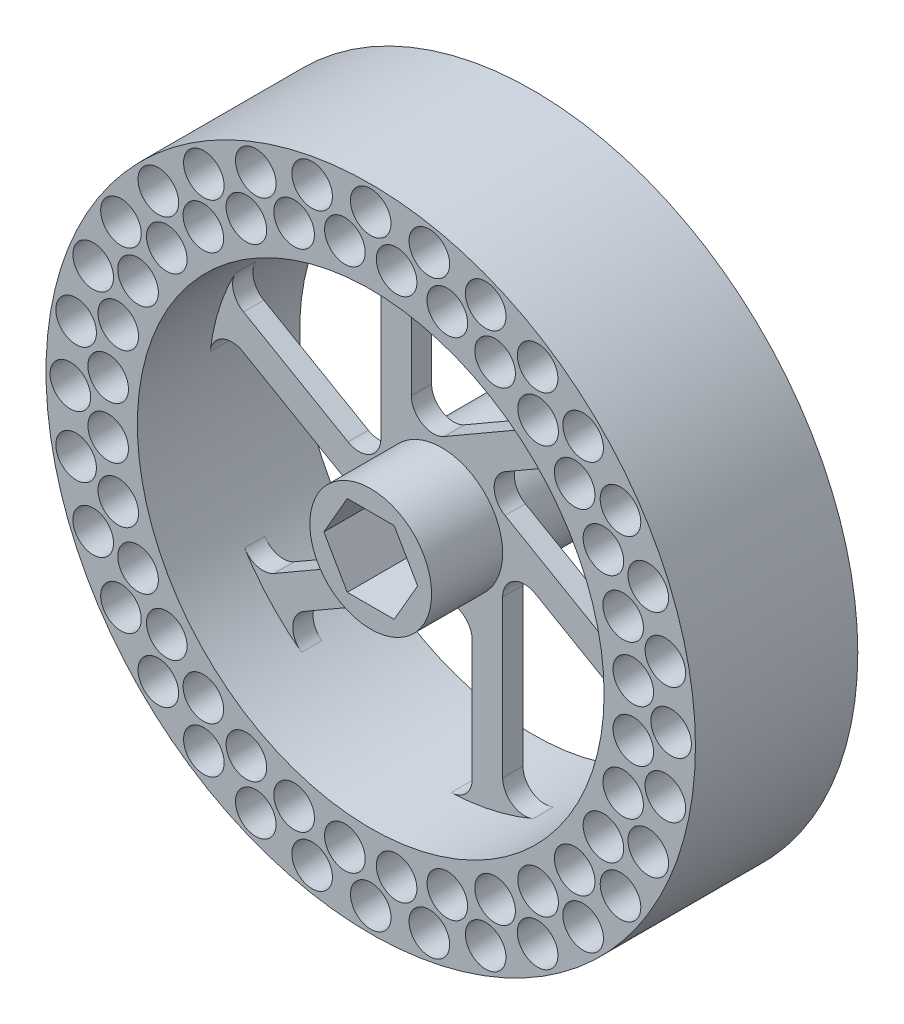
SolidWorks part; units mm, degrees
ref_plane "Front Plane" through (0, 0, 0) normal (0, 0, 1) x (1, 0, 0)
ref_plane "Top Plane" through (0, 0, 0) normal (0, 1, 0) x (1, 0, 0)
ref_plane "Right Plane" through (0, 0, 0) normal (1, 0, 0) x (0, 0, -1)
sketch "Sketch1" plane through (0, 0, 0) normal (0, 0, 1) x (1, 0, 0)
  line L1 (-3.6662, 6.35) -> (-7.3323, 0)
  line L2 (-7.3323, 0) -> (-3.6662, -6.35)
  line L3 (-3.6662, -6.35) -> (3.6662, -6.35)
  line L4 (3.6662, -6.35) -> (7.3323, 0)
  line L5 (7.3323, 0) -> (3.6662, 6.35)
  line L6 (3.6662, 6.35) -> (-3.6662, 6.35)
  circle A0 centre (0, 0) radius 6.35 construction
  circle A1 centre (0, 0) radius 46.9945 construction
  circle A2 centre (0, 0) radius 50.8
  dimension "D1" = 93.9889
  dimension "D2" = 101.6
  dimension "D3" = 12.7
extrude "Boss-Extrude1" add sketch "Sketch1" along normal mid plane 25.4
sketch "Sketch2" plane through (0, 0, 12.7) normal (0, 0, 1) x (1, 0, 0)
  circle A0 centre (0, 46.9945) radius 3.175
  circle A1 centre (0, 0) radius 46.9945 construction
  dimension "D1" = 6.35
extrude "Cut-Extrude1" cut sketch "Sketch2" against normal through all
pattern_circular "CirPattern1" count 32 over 360 about axis through (0, 0, 12.7) along (0, 0, -1) of "Cut-Extrude1"
sketch "Sketch3" plane through (0, 0, 12.7) normal (0, 0, 1) x (1, 0, 0)
  line L0 (0, 46.9945) -> (4.0457, 41.0762) construction
  line L1 (4.0457, 41.0762) -> (9.1682, 46.0915) construction
  circle A0 centre (4.0457, 41.0762) radius 3.175
  circle A1 centre (9.1682, 46.0915) radius 3.175 construction
  circle A2 centre (0, 0) radius 41.275 construction
  dimension "D1" = 82.55
extrude "Cut-Extrude2" cut sketch "Sketch3" against normal through all
pattern_circular "CirPattern2" count 32 every 11.25 about axis through (0, 0, 12.7) along (0, 0, -1) of "Cut-Extrude2"
sketch "Sketch4" plane through (0, 0, 12.7) normal (0, 0, 1) x (1, 0, 0)
  circle A0 centre (0, 0) radius 36.5125
  circle A1 centre (0, 0) radius 9.525
  dimension "D1" = 73.025
  dimension "D2" = 19.05
extrude "Cut-Extrude3" cut sketch "Sketch4" against normal through all
sketch "Sketch5" plane through (0, 0, 0) normal (0, 0, 1) x (1, 0, 0)
  line L0 (-9.525, 0) -> (-9.525, 35.2482)
  line L1 (-4.7625, 8.2489) -> (-4.7625, 36.2006)
  circle A0 centre (0, 0) radius 9.525 construction
  circle A1 centre (0, 0) radius 36.5125 construction
  arc A2 (-4.7625, 36.2006) -> (-9.525, 35.2482) centre (0, 0) ccw
  arc A3 (-4.7625, 8.2489) -> (-9.525, 0) centre (0, 0) ccw
  dimension "D1" = 4.7625
extrude "Boss-Extrude2" add sketch "Sketch5" along normal mid plane 3.175
pattern_circular "CirPattern3" count 6 over 360 about axis through (0, 0, 12.7) along (0, 0, -1) of "Boss-Extrude2"
fillet "Fillet1" radius 3.429 18 edges at (33.7319, -13.9758, 0) (35.2884, -9.3752, 0) (28.9694, 22.2247, 0) (-9.525, 35.2482, 0) (25.7634, 25.873, 0) (-4.7625, 36.2006, 0) (-35.2884, 9.3752, 0) (-33.7319, 13.9758, 0) (-28.9694, -22.2247, 0) (-25.7634, -25.873, 0) (9.525, -35.2482, 0) (4.7625, -36.2006, 0) (-9.525, 0, 0) (-4.7625, -8.2489, 0) (4.7625, -8.2489, 0) (9.525, 0, 0) (4.7625, 8.2489, 0) (-4.7625, 8.2489, 0)
